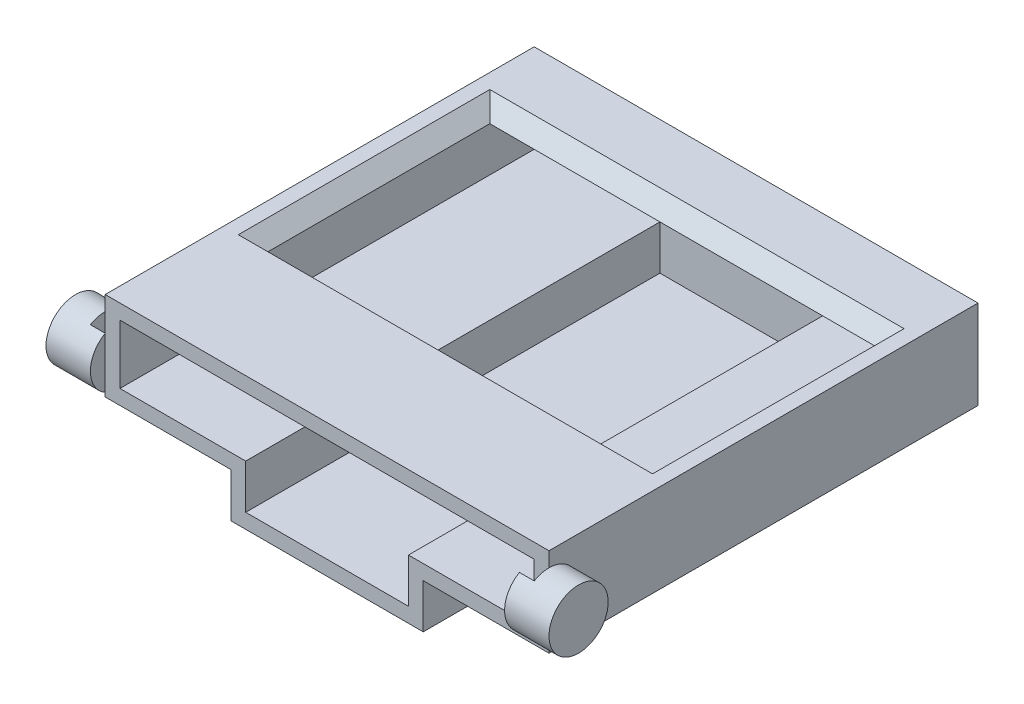
SolidWorks part; units mm, degrees
ref_plane "Plan de face" through (0, 0, 0) normal (0, 0, 1) x (1, 0, 0)
ref_plane "Plan de dessus" through (0, 0, 0) normal (0, 1, 0) x (1, 0, 0)
ref_plane "Plan de droite" through (0, 0, 0) normal (1, 0, 0) x (0, 0, -1)
sketch "Esquisse1" plane through (0, 0, 0) normal (0, 1, 0) x (1, 0, 0)
  line L1 (0, 0) -> (30, 0)
  line L2 (0, 0) -> (0, 29)
  line L3 (0, 29) -> (30, 29)
  line L4 (30, 0) -> (30, 29)
  dimension "D1" = 29
  dimension "D2" = 30
extrude "Boss.-Extru.1" add sketch "Esquisse1" along normal blind 6
shell "Coque1" thickness 1 removed face at (15, 3, 0)
sketch "Esquisse2" plane through (0, 6, 0) normal (0, 1, 0) x (1, 0, 0)
  line L0 (30, 29) -> (0, 29) construction
  line L1 (2, 24) -> (28, 24)
  line L2 (2, 24) -> (2, 9)
  line L3 (2, 9) -> (28, 9)
  line L4 (28, 24) -> (28, 9)
  line L5 (0, 0) -> (30, 0) construction
  point P6 (15, 24)
  point P7 (15, 29)
  dimension "D1" = 0
  dimension "D2" = 9
  dimension "D3" = 26
  dimension "D4" = 15
extrude "Enlèv. mat.-Extru.1" cut sketch "Esquisse2" against normal up to next
sketch "Esquisse3" plane through (0, 0, 0) normal (0, -1, 0) x (1, 0, 0)
  line L0 (0, 0) -> (30, 0) construction
  line L1 (8.5, 0) -> (21.5, 0)
  line L2 (8.5, 0) -> (8.5, -29)
  line L3 (8.5, -29) -> (21.5, -29)
  line L4 (21.5, 0) -> (21.5, -29)
  line L5 (30, -29) -> (0, -29) construction
  point P8 (15, 0)
  point P9 (15, 0)
  dimension "D1" = 0
  dimension "D2" = 13
extrude "Boss.-Extru.2" add sketch "Esquisse3" along normal blind 3
sketch "Esquisse5" plane through (0, 1, 0) normal (0, 1, 0) x (1, 0, 0)
  line L0 (1, 0) -> (29, 0) construction
  line L1 (20.5, 0) -> (9.5, 0)
  line L2 (20.5, 0) -> (20.5, 28)
  line L3 (20.5, 28) -> (9.5, 28)
  line L4 (9.5, 0) -> (9.5, 28)
  line L5 (0, 0) -> (30, 0) construction
  point P6 (15, 0)
  point P9 (15, 0)
  dimension "D1" = 28
  dimension "D2" = 11
  dimension "D3" = 0
extrude "Enlèv. mat.-Extru.2" cut sketch "Esquisse5" against normal blind 3
sketch "Esquisse6" plane through (30, 0, 0) normal (1, 0, 0) x (0, 0, -1)
  line L0 (0, 6) -> (0, 0) construction
  circle A0 centre (0, 3) radius 2
  dimension "D1" = 4
extrude "Boss.-Extru.3" add sketch "Esquisse6" along normal blind 2 and the other way blind 1
sketch "Esquisse7" plane through (0, 0, 0) normal (-1, 0, 0) x (0, 0, 1)
  line L0 (0, 6) -> (0, 0) construction
  circle A0 centre (0, 3) radius 2
  dimension "D1" = 4
extrude "Boss.-Extru.4" add sketch "Esquisse7" along normal blind 2 and the other way blind 1
fillet "Congé1" [suppressed] radius 2
fillet "Congé2" [suppressed] radius 2
fillet "Congé3" [suppressed] radius 1
chamfer "Chanfrein1" distance 1 angle 45 4 edges at (15, 6, -24) (28, 6, -16.5) (15, 6, -9) (2, 6, -16.5)
sketch "Esquisse8" plane through (0, 0, 0) normal (0, 0, 1) x (1, 0, 0)
  line L0 (20.5, -2) -> (20.5, 1) construction
  line L1 (20.5, 1) -> (29, 1) construction
  line L2 (9.5, -2) -> (9.5, 1) construction
  line L3 (1, 1) -> (9.5, 1) construction
  circle A0 centre (22.5, -1) radius 2
  circle A1 centre (7.5, -1) radius 2
  point P8 (20.5, -0.5)
  dimension "D1" = 4
  dimension "D6" = 4
  dimension "D2" = 2
  dimension "D3" = 2
  dimension "D4" = 2
  dimension "D5" = 2
extrude "Boss.-Extru.5" [suppressed] add sketch "Esquisse8" against normal blind 10
sketch "Esquisse9" [suppressed] plane through (0, 0, 0) normal (0, 0, 1) x (1, 0, 0)
  circle A0 centre (22.5, -1) radius 1.25
  circle A1 centre (7.5, -1) radius 1.25
  dimension "D1" = 2.5
  dimension "D2" = 2.5
extrude "Enlèv. mat.-Extru.3" [suppressed] cut sketch "Esquisse9" against normal blind 9
sketch "Esquisse10" [suppressed] plane through (29, 0, 0) normal (-1, 0, 0) x (0, 0, 1)
  line L1 (0, 1) -> (1, 1)
  line L2 (0, 1) -> (0, 4.7321)
  line L3 (0, 4.7321) -> (1, 4.7321)
  line L4 (1, 1) -> (1, 4.7321)
  arc A0 (0, 1) -> (0, 5) centre (0, 3) ccw construction
  dimension "D1" = 1
  dimension "4" = 3.7321
sketch "Esquisse11" plane through (29, 0, 0) normal (-1, 0, 0) x (0, 0, 1)
  line L0 (0, 1) -> (0, 0) construction
  line L1 (1, 0.5032) -> (0, 0.5032)
  line L2 (1, 0.5032) -> (1, 6.3702)
  line L3 (1, 6.3702) -> (0, 6.3702)
  line L4 (0, 0.5032) -> (0, 6.3702)
  point P6 (0, 0.5)
  dimension "D1" = 0
  dimension "D2" = 1
extrude "Enlèv. mat.-Extru.5" cut sketch "Esquisse11" against normal blind 1
sketch "Esquisse12" plane through (1, 0, 0) normal (1, 0, 0) x (0, 0, -1)
  line L0 (0, 1) -> (0, 0) construction
  line L1 (0, -1.8262) -> (-1, -1.8262)
  line L2 (0, -1.8262) -> (0, 7.4168)
  line L3 (0, 7.4168) -> (-1, 7.4168)
  line L4 (-1, -1.8262) -> (-1, 7.4168)
  point P6 (0, 0.5)
  dimension "D1" = 0
  dimension "D2" = 1
extrude "Enlèv. mat.-Extru.6" cut sketch "Esquisse12" against normal blind 1
